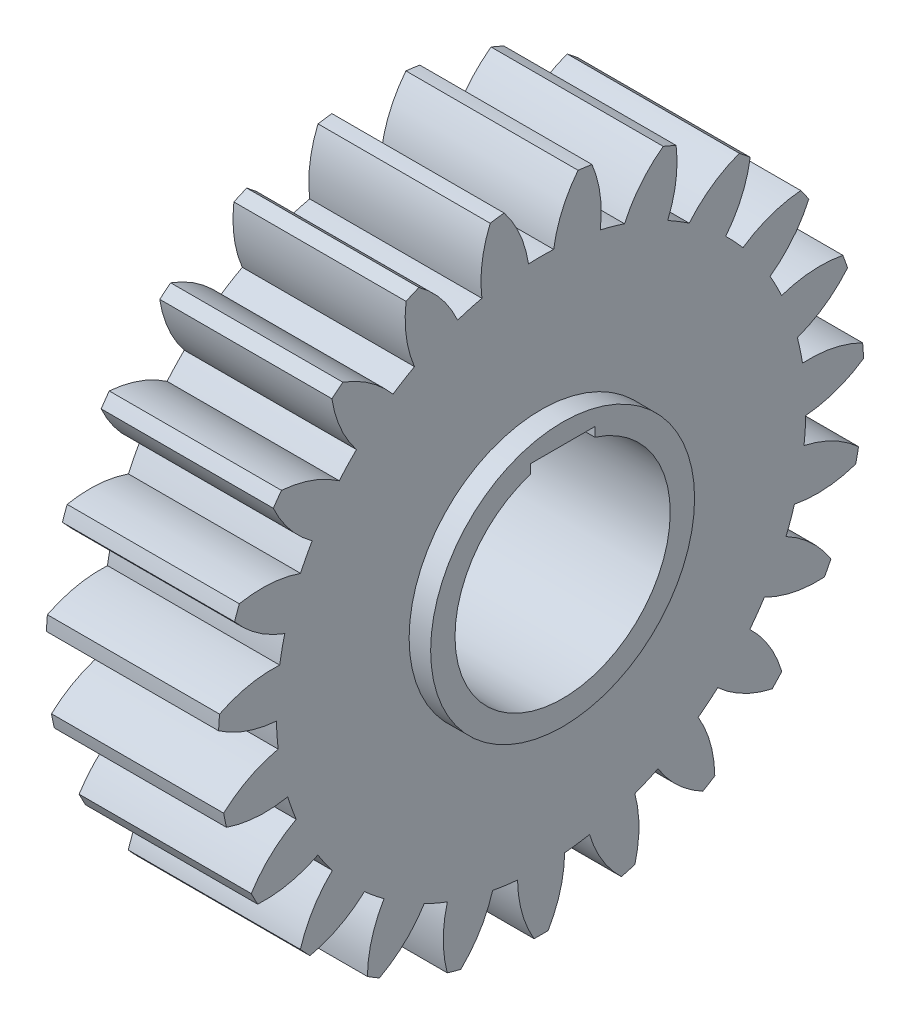
SolidWorks part; units mm, degrees
ref_plane "Plane1" through (0, 0, 0) normal (0, 0, 1) x (1, 0, 0)
ref_plane "Plane2" through (0, 0, 0) normal (0, 1, 0) x (1, 0, 0)
ref_plane "Plane3" through (0, 0, 0) normal (1, 0, 0) x (0, 0, -1)
sketch "HoldingSke" plane through (0, 0, 0) normal (0, 1, 0) x (1, 0, 0)
  line L0 (0, 0) -> (1.5342, -0.6512)
  line L1 (-15, 0) -> (100, 0) construction
  line L2 (0, 0) -> (-2.1039, 2.3779)
  line L3 (0, 0) -> (-11.863, 4.5341)
  line L4 (0, 0) -> (7.9495, 3.3744)
  line L5 (0, 0) -> (-46.8476, -17.4728)
  line L6 (0, 0) -> (-3.3159, -2.2372)
  line L7 (-2.1039, 2.3779) -> (8.6586, 51.2059)
  line L8 (-76.2, 54.61) -> (-75.3, 54.61)
  line L9 (-71.009, 38.7566) -> (-53.1078, 45.2721)
  line L10 (-76.2, 71.12) -> (104.1128, 71.12)
  line L11 (0, 0) -> (-4, 0)
  line L12 (-76.2, 101.6) -> (-76.177, 101.6)
  line L13 (24.9733, 27.94) -> (52.9518, 28.4284)
  line L14 (24.9733, 27.94) -> (24.9743, 27.94)
  line L15 (24.9733, 27.94) -> (100.4006, 29.5858)
  line L16 (-63.627, -0.6) -> (-12.827, -0.6)
  circle A0 centre (0, 0) radius 2.5
  circle A1 centre (0, 0) radius 6.149
  circle A2 centre (0, 0) radius 37.5
  circle A3 centre (0, 0) radius 2.5
  dimension "MHD" = 12.298
  dimension "Hub_dia" = 75
  dimension "Bore" = 5
  dimension "MBD" = 5
  dimension "Num_teeth" = 23
  dimension "Pitch_radius" = 180.3128
  dimension "Pitch" = 1.6667
  dimension "Width" = 4
  dimension "Overall_len" = 50
  dimension "Show_teeth" = 23
  dimension "Thickness" = 4
  dimension "OAL" = 50.0001
  dimension "T_dim" = 0.9
  dimension "Ap" = 20
  dimension "H" = 19.05
  dimension "Backlash" = 0.023
  dimension "Addendum_fac" = 1
  dimension "Dedendum_fac" = 1.25
  dimension "Clearance_fac" = 0.25
  dimension "Dedendum_add" = 0.001
  dimension "Module" = 0.6
sketch "BasProSke" plane through (0, 0, 0) normal (0, 1, 0) x (1, 0, 0)
  line L0 (-10, 0) -> (60, 0) construction
  line L1 (0, 0) -> (0, 7.5)
  line L2 (0, 0) -> (4, 0)
  line L3 (4, 0) -> (4, 7.5)
  line L4 (4, 7.5) -> (0, 7.5)
  dimension "Diameter" = 15
  dimension "Thickness" = 4
revolve "Base-Revolve" add sketch "BasProSke" angle 360 about L0
sketch "TooCutSke" plane through (0, 0, 0) normal (1, 0, 0) x (0, 0, -1)
  line L1 (0, 0) -> (0, 107) construction
  line L2 (0, 0) -> (-0.5111, 6.881) construction
  line L3 (0, 0) -> (-1.8754, 13.6448) construction
  line L4 (-0.5111, 6.881) -> (-0.9377, 6.8224) construction
  arc A0 (0.2925, 6.142) -> (-0.2925, 6.142) centre (0, 0) ccw
  arc A1 (0.8782, 7.474) -> (-0.8782, 7.474) centre (0, 0) ccw
  circle A2 centre (0, 0) radius 6.9 construction
  circle A3 centre (0, 0) radius 6.4839 construction
  arc A4 (-0.2925, 6.142) -> (-0.8782, 7.474) centre (-3.0225, 5.7363) ccw
  arc A5 (0.8782, 7.474) -> (0.2925, 6.142) centre (3.0225, 5.7363) ccw
  dimension "Root_dia" = 12.298
  dimension "Overcut_dia" = 15.0508
  dimension "Pitch_dia" = 13.8
  dimension "Base_dia" = 12.9678
  dimension "Flank_rad" = 2.76
  dimension "Half_ang" = 7.826
  dimension "Half_CT" = 0.4306
extrude "ToothCut" cut sketch "TooCutSke" along normal through all
fillet "Breaks" [suppressed] radius 0.012 tangent propagation no
fillet "RootFillets" [suppressed] radius 0.151
pattern_circular "TeethCuts" count 23 every 15.652 about axis through (-10, 0, 0) along (1, 0, 0) of "ToothCut", "RootFillets", "Breaks"
sketch "HubNeaOneSke" plane through (0, 0, 0) normal (-1, 0, 0) x (0, 0, 1)
  circle A0 centre (0, 0) radius 6.149
  dimension "Diameter" = 12.298
extrude "HubNearOne" [suppressed] add sketch "HubNeaOneSke" along normal blind 46.0001
sketch "HubNeaBotSke" plane through (0, 0, 0) normal (-1, 0, 0) x (0, 0, 1)
  circle A0 centre (0, 0) radius 6.149
  dimension "Diameter" = 12.298
extrude "HubNearBoth" [suppressed] add sketch "HubNeaBotSke" along normal blind 23
ref_plane "FarPln" through (4, 0, 0) normal (1, 0, 0) x (0, 0, -1)
sketch "HubFarSke" plane through (4, 0, 0) normal (1, 0, 0) x (0, 0, -1)
  circle A0 centre (0, 0) radius 6.149
  dimension "Diameter" = 12.298
extrude "HubFar" [suppressed] add sketch "HubFarSke" along normal blind 23
sketch "BorSke" plane through (0, 0, 0) normal (1, 0, 0) x (0, 0, -1)
  circle A0 centre (0, 0) radius 2.5
  dimension "Diameter" = 5
extrude "Bore" cut sketch "BorSke" along normal mid plane 100.0001
sketch "KeySke" plane through (0, 0, 0) normal (1, 0, 0) x (0, 0, -1)
  line L0 (-1, 0) -> (-1, 3.4)
  line L1 (-1, 3.4) -> (1, 3.4)
  line L2 (1, 3.4) -> (1, 0)
  line L3 (0, 0) -> (0, 34) construction
  line L4 (-1, 0) -> (1, 0)
  dimension "Offset" = 3.4
  dimension "Width" = 2
extrude "Keyway" [suppressed] cut sketch "KeySke" along normal mid plane 100.0001
pattern_circular "Keyway2" [suppressed] count 2 every 90 about axis through (-10, 0, 0) along (1, 0, 0)
sketch "Sketch1" plane through (4, 0, 0) normal (1, 0, 0) x (0, 0, -1)
  circle A0 centre (0, 0) radius 2.5
  circle A1 centre (0, 0) radius 3.0659
extrude "Extrude1" add sketch "Sketch1" along normal blind 0.5 and the other way blind 4.5
sketch "Sketch2" plane through (4.5, 0, 0) normal (1, 0, 0) x (0, 0, -1)
  line L0 (0, 3.5289) -> (0, -1.8075) construction
  line L1 (-0.75, 2.6) -> (0.75, 2.6)
  line L2 (-0.75, 2.6) -> (-0.75, 0)
  line L3 (-0.75, 0) -> (0.75, 0)
  line L4 (0.75, 2.6) -> (0.75, 0)
  dimension "D1" = 1.5
  dimension "D2" = 2.6
extrude "Cut-Extrude1" cut sketch "Sketch2" against normal blind 5.5
equation "' \"Module@HoldingSke\" = 6.35"
equation "' \"Num_teeth@HoldingSke\" = 12"
equation "' \"Ap@HoldingSke\" =  20"
equation "' \"Width@HoldingSke\" = 0.5 * 25.4"
equation "' \"Hub_dia@HoldingSke\"= 1 * 25.4"
equation "' \"Overall_len@HoldingSke\" = 1.0 * 25.4"
equation "' \"Bore@HoldingSke\" = 0.75 * 25.4"
equation "' \"T_dim@HoldingSke\" = 0.1 * 25.4"
equation "' \"Width@KeySke\" = 0.25 * 25.4"
equation "' \"Show_teeth@HoldingSke\" = 13"
equation "' \"Backlash@HoldingSke\" = 0.009 * 25.4"
equation "' \"Addendum_fac@HoldingSke\" = 1.0"
equation "' \"Dedendum_fac@HoldingSke\" = 1.25"
equation "' \"Dedendum_add@HoldingSke\" = 0.00005 * 25.4"
equation "' \"Clearance_fac@HoldingSke\" = 0.25"
equation "\"Pitch@HoldingSke\" = 1 / \"Module@HoldingSke\""
equation "\"Overcut_dia@TooCutSke\" = (\"Num_teeth@HoldingSke\" + 2 * \"Addendum_fac@HoldingSke\") / \"Pitch@HoldingSke\" + 0.002 * 25.4"
equation "\"Pitch_dia@TooCutSke\" = \"Num_teeth@HoldingSke\" / \"Pitch@HoldingSke\""
equation "\"Base_dia@TooCutSke\" = \"Num_teeth@HoldingSke\" / \"Pitch@HoldingSke\" * cos((\"Ap@HoldingSke\"  * 3.14159265 / 180))"
equation "\"Root_dia@TooCutSke\" = (\"Num_teeth@HoldingSke\" + 2) / \"Pitch@HoldingSke\" - 2 * (\"Addendum_fac@HoldingSke\" + \"Dedendum_fac@HoldingSke\") / \"Pitch@HoldingSke\" - \"Dedendum_add@HoldingSke\" * 2"
equation "\"Half_ang@TooCutSke\" = 180 / \"Num_teeth@HoldingSke\""
equation "\"Half_CT@TooCutSke\" = \"Num_teeth@HoldingSke\" / \"Pitch@HoldingSke\" * sin((3.14159265 / 2 / \"Num_teeth@HoldingSke\")) / 2 - 7 * \"Backlash@HoldingSke\" / 4"
equation "\"Flank_rad@TooCutSke\" = \"Num_teeth@HoldingSke\" / \"Pitch@HoldingSke\" / 5"
equation "\"Radius@RootFillets\" = \"Clearance_fac@HoldingSke\" / \"Pitch@HoldingSke\" + \"Dedendum_add@HoldingSke\""
equation "\"Break_rad@Breaks\" = 0.02 / \"Pitch@HoldingSke\""
equation "\"Thickness@HoldingSke\" = \"Width@HoldingSke\""
equation "\"OAL@HoldingSke\" = \"Thickness@HoldingSke\""
equation "\"MHD@HoldingSke\" = (\"Num_teeth@HoldingSke\" + 2) / \"Pitch@HoldingSke\" - 2 * (\"Addendum_fac@HoldingSke\" + \"Dedendum_fac@HoldingSke\")  / \"Pitch@HoldingSke\" - \"Dedendum_add@HoldingSke\" * 2"
equation "\"MBD@HoldingSke\" = (\"Num_teeth@HoldingSke\" + 2) / \"Pitch@HoldingSke\" - 2 * (\"Addendum_fac@HoldingSke\" + \"Dedendum_fac@HoldingSke\")  / \"Pitch@HoldingSke\" - \"Dedendum_add@HoldingSke\" * 2 - 0.002 * 25.4"
equation "\"MHD@HoldingSke\" = ((sgn( \"MHD@HoldingSke\" - \"Hub_dia@HoldingSke\" )-1)*( \"MHD@HoldingSke\" - \"Hub_dia@HoldingSke\" ))/-2+ \"Hub_dia@HoldingSke\""
equation "\"MBD@HoldingSke\" = ((sgn( \"MBD@HoldingSke\" - \"Bore@HoldingSke\" )-1)*( \"MBD@HoldingSke\" - \"Bore@HoldingSke\" ))/-2+ \"Bore@HoldingSke\""
equation "\"OAL@HoldingSke\" = ((sgn( \"OAL@HoldingSke\" - \"Overall_len@HoldingSke\" )+1)*( \"OAL@HoldingSke\" - \"Overall_len@HoldingSke\" ))/2 + \"Overall_len@HoldingSke\" + 0.000002 * 25.4"
equation "\"Num_teeth@TeethCuts\" = int( \"Show_teeth@HoldingSke\" ) + 1"
equation "\"Num_teeth@TeethCuts\" = ((sgn( \"Num_teeth@TeethCuts\" - \"Num_teeth@HoldingSke\" )-1)*( \"Num_teeth@TeethCuts\" - \"Num_teeth@HoldingSke\" ))/-2+ \"Num_teeth@HoldingSke\""
equation "\"Num_teeth@TeethCuts\" = ((sgn( \"Num_teeth@TeethCuts\" - 2.0)+1)*( \"Num_teeth@TeethCuts\" - 2.0))/2 +2.0"
equation "\"Angle@TeethCuts\" = 360.0 / \"Num_teeth@HoldingSke\""
equation "\"Diameter@BasProSke\" = (\"Num_teeth@HoldingSke\" + 2 * \"Addendum_fac@HoldingSke\") / \"Pitch@HoldingSke\""
equation "\"Thickness@BasProSke\"  = \"Thickness@HoldingSke\""
equation "' \"Fillet_rad@BasProSke\" =  \"Thickness@HoldingSke\" * 0.05"
equation "\"MHD@HoldingSke\" = ((sgn( \"MHD@HoldingSke\" - \"Root_dia@TooCutSke\" )-1)*( \"MHD@HoldingSke\" - \"Root_dia@TooCutSke\" ))/-2+ \"Root_dia@TooCutSke\""
equation "\"Diameter@HubNeaOneSke\" = \"MHD@HoldingSke\""
equation "\"Length@HubNearOne\" = \"OAL@HoldingSke\" - \"Thickness@BasProSke\""
equation "\"Diameter@HubNeaBotSke\" = \"MHD@HoldingSke\""
equation "\"Length@HubNearBoth\" = ( \"OAL@HoldingSke\" - \"Thickness@BasProSke\" ) / 2.0"
equation "\"Thickness@FarPln\" = \"Thickness@BasProSke\""
equation "\"Diameter@HubFarSke\" = \"MHD@HoldingSke\""
equation "\"Length@HubFar\" = ( \"OAL@HoldingSke\" - \"Thickness@BasProSke\" ) / 2.0"
equation "\"Diameter@BorSke\" = \"MBD@HoldingSke\""
equation "\"D1@Bore\" = \"OAL@HoldingSke\" * 2.0"
equation "\"D1@Keyway\" = \"OAL@HoldingSke\" * 2.0"
equation "\"Offset@KeySke\" = \"T_dim@HoldingSke\" + \"MBD@HoldingSke\" / 2.0"
